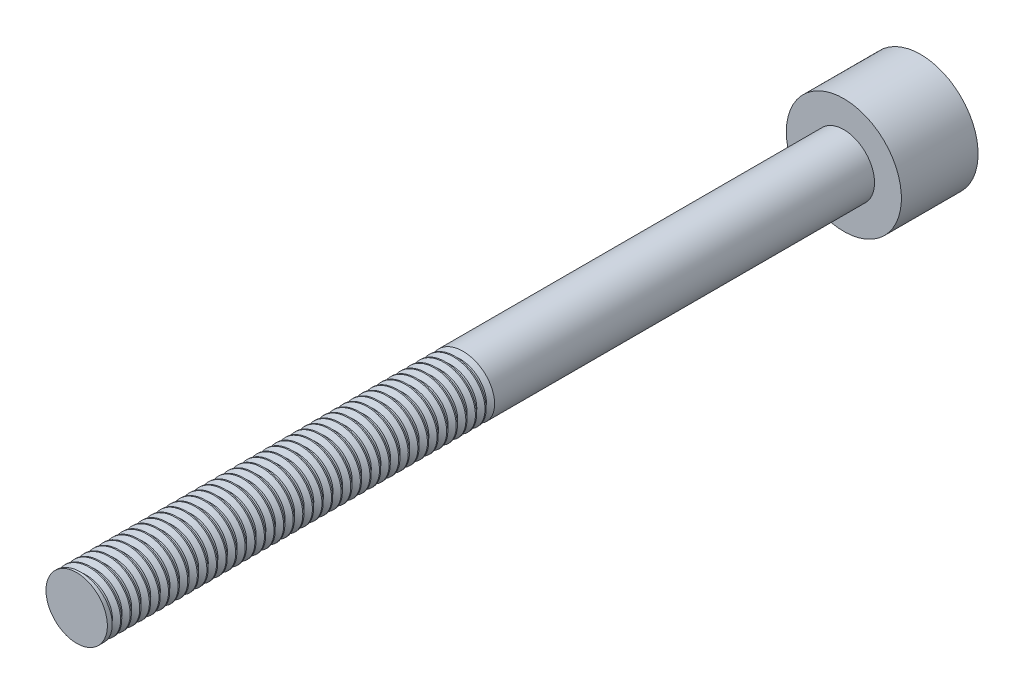
SolidWorks part; units mm, degrees
material "Dövülebilir Dökme Demir"
ref_plane "Ön Düzlem" through (0, 0, 0) normal (0, 0, 1) x (1, 0, 0)
ref_plane "Üst Düzlem" through (0, 0, 0) normal (0, 1, 0) x (1, 0, 0)
ref_plane "Sağ Düzlem" through (0, 0, 0) normal (1, 0, 0) x (0, 0, -1)
sketch "Sketch1" plane through (0, 0, 0) normal (0, 0, 1) x (1, 0, 0)
  circle A0 centre (0, 0) radius 4
  dimension "D1" = 8
extrude "Boss-Extrude1" add sketch "Sketch1" along normal blind 110
sketch "Sketch2" plane through (0, 0, 0) normal (0, 0, -1) x (-1, 0, 0)
  circle A0 centre (0, 0) radius 7.5
extrude "Boss-Extrude2" add sketch "Sketch2" against normal blind 10
sketch "Sketch3" plane through (0, 0, 0) normal (0, 0, -1) x (-1, 0, 0)
  line L1 (1.9775, -3.6295) -> (4.132, -0.1022)
  line L2 (4.132, -0.1022) -> (2.1545, 3.5273)
  line L3 (2.1545, 3.5273) -> (-1.9775, 3.6295)
  line L4 (-1.9775, 3.6295) -> (-4.132, 0.1022)
  line L5 (-4.132, 0.1022) -> (-2.1545, -3.5273)
  line L6 (-2.1545, -3.5273) -> (1.9775, -3.6295)
  circle A0 centre (0, 0) radius 3.5795 construction
extrude "Cut-Extrude1" cut sketch "Sketch3" against normal blind 5
thread "Thread1" pitch 1.25 method cut profile "Thread Profile1" start angle 0, offset 0, length 50, pitch 1.25, diameter 8
ref_plane "Plane1" through (-4, 0, 110) normal (0, -1, 0) x (-1, 0, 0)
sketch "Thread Profile1" plane through (-4, 0, 110) normal (0, -1, 0) x (-1, 0, 0)
  line L0 (0, 0) -> (0, 1.25) construction
  line L11 (0, 0) -> (0, 1.0937)
  line L12 (0, 1.0937) -> (-0.6766, 0.7031)
  line L13 (-0.6766, 0.7031) -> (-0.6766, 0.3906)
  line L15 (-0.6766, 0.3906) -> (0, 0)
  line L17 (-0.6766, 0.5469) -> (0, 0.5469) construction
  point P2 (0, 0)
  dimension "Pitch" = 1.25
  dimension "Profile_Angle" = 60
  dimension "Profile_Land" = 0.3125
  dimension "Profile_Height" = 0.6766
